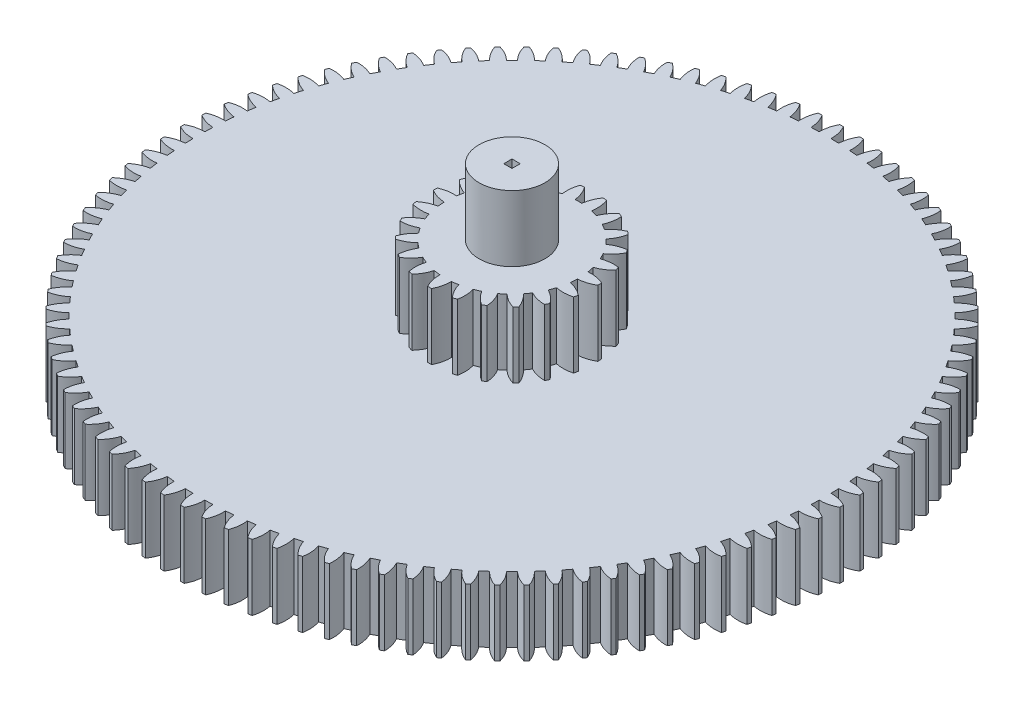
SolidWorks part; units mm, degrees
ref_plane "Front Plane" through (0, 0, 0) normal (0, 0, 1) x (1, 0, 0)
ref_plane "Top Plane" through (0, 0, 0) normal (0, 1, 0) x (1, 0, 0)
ref_plane "Right Plane" through (0, 0, 0) normal (1, 0, 0) x (0, 0, -1)
sketch "Sketch1" plane through (0, 0, 0) normal (0, 1, 0) x (1, 0, 0)
  arc A0 (-1.1228, 2.2337) -> (-1.1773, 2.2054) centre (0, 0) ccw
  arc A1 (-2.1122, 0.8038) -> (-2.1457, 0.7095) centre (0, 0) ccw
  arc A2 (0.05, 2.2594) -> (0.14, 2.4961) centre (0.4546, 2.241) cw
  arc A3 (-0.05, 2.2594) -> (-0.14, 2.4961) centre (-0.4546, 2.241) ccw
  arc A4 (0.3572, 2.2316) -> (0.4786, 2.4538) centre (0.7555, 2.1582) cw
  arc A5 (0.2581, 2.2452) -> (0.2012, 2.4919) centre (-0.1453, 2.282) ccw
  arc A6 (0.6577, 2.1622) -> (0.8082, 2.3657) centre (1.0424, 2.0352) cw
  arc A7 (0.5614, 2.1892) -> (0.5386, 2.4413) centre (0.1668, 2.2805) ccw
  arc A8 (0.946, 2.0525) -> (1.1228, 2.2337) centre (1.3098, 1.8743) cw
  arc A9 (0.8543, 2.0923) -> (0.866, 2.3452) centre (0.4758, 2.2366) ccw
  arc A10 (1.2167, 1.9045) -> (1.4165, 2.06) centre (1.5528, 1.6785) cw
  arc A11 (1.1313, 1.9565) -> (1.1773, 2.2054) centre (0.7759, 2.151) ccw
  arc A12 (1.4647, 1.7211) -> (1.6838, 1.8479) centre (1.7669, 1.4514) cw
  arc A13 (1.3871, 1.7842) -> (1.4666, 2.0246) centre (1.0616, 2.0253) ccw
  arc A14 (1.6854, 1.5057) -> (1.9198, 1.6014) centre (1.9481, 1.1973) cw
  arc A15 (1.6172, 1.5787) -> (1.7287, 1.806) centre (1.3275, 1.8619) ccw
  arc A16 (1.8747, 1.2621) -> (2.12, 1.3251) centre (2.093, 0.9209) cw
  arc A17 (1.8171, 1.3438) -> (1.9585, 1.5538) centre (1.5686, 1.6638) ccw
  arc A18 (2.0291, 0.9951) -> (2.2806, 1.0241) centre (2.1989, 0.6273) cw
  arc A19 (1.9831, 1.0839) -> (2.1518, 1.2727) centre (1.7806, 1.4347) ccw
  arc A20 (2.1457, 0.7095) -> (2.3988, 0.704) centre (2.2638, 0.3221) cw
  arc A21 (2.1122, 0.8038) -> (2.3051, 0.9678) centre (1.9593, 1.1788) ccw
  arc A22 (2.2224, 0.4107) -> (2.4724, 0.3708) centre (2.2866, 0.0108) cw
  arc A23 (2.202, 0.5087) -> (2.4154, 0.6449) centre (2.1016, 0.9011) ccw
  arc A24 (2.2576, 0.1043) -> (2.4998, 0.0307) centre (2.2668, -0.3006) cw
  arc A25 (2.2508, 0.2041) -> (2.4807, 0.31) centre (2.2047, 0.6065) ccw
  arc A26 (2.2508, -0.2041) -> (2.4807, -0.31) centre (2.2047, -0.6065) cw
  arc A27 (2.2576, -0.1043) -> (2.4998, -0.0307) centre (2.2668, 0.3006) ccw
  arc A28 (2.202, -0.5087) -> (2.4154, -0.6449) centre (2.1016, -0.9011) cw
  arc A29 (2.2224, -0.4107) -> (2.4724, -0.3708) centre (2.2866, -0.0108) ccw
  arc A30 (2.1122, -0.8038) -> (2.3051, -0.9678) centre (1.9593, -1.1788) cw
  arc A31 (2.1457, -0.7095) -> (2.3988, -0.704) centre (2.2638, -0.3221) ccw
  arc A32 (1.9831, -1.0839) -> (2.1518, -1.2727) centre (1.7806, -1.4347) cw
  arc A33 (2.0291, -0.9951) -> (2.2806, -1.0241) centre (2.1989, -0.6273) ccw
  arc A34 (1.8171, -1.3438) -> (1.9585, -1.5538) centre (1.5686, -1.6638) cw
  arc A35 (1.8747, -1.2621) -> (2.12, -1.3251) centre (2.093, -0.9209) ccw
  arc A36 (1.6172, -1.5787) -> (1.7287, -1.806) centre (1.3275, -1.8619) cw
  arc A37 (1.6854, -1.5057) -> (1.9198, -1.6014) centre (1.9481, -1.1973) ccw
  arc A38 (1.3871, -1.7842) -> (1.4666, -2.0246) centre (1.0616, -2.0253) cw
  arc A39 (1.4647, -1.7211) -> (1.6838, -1.8479) centre (1.7669, -1.4514) ccw
  arc A40 (1.1313, -1.9565) -> (1.1773, -2.2054) centre (0.7759, -2.151) cw
  arc A41 (1.2167, -1.9045) -> (1.4165, -2.06) centre (1.5528, -1.6785) ccw
  arc A42 (0.8543, -2.0923) -> (0.866, -2.3452) centre (0.4758, -2.2366) cw
  arc A43 (0.946, -2.0525) -> (1.1228, -2.2337) centre (1.3098, -1.8743) ccw
  arc A44 (0.5614, -2.1892) -> (0.5386, -2.4413) centre (0.1668, -2.2805) cw
  arc A45 (0.6577, -2.1622) -> (0.8082, -2.3657) centre (1.0424, -2.0352) ccw
  arc A46 (0.2581, -2.2452) -> (0.2012, -2.4919) centre (-0.1453, -2.282) cw
  arc A47 (0.3572, -2.2316) -> (0.4786, -2.4538) centre (0.7555, -2.1582) ccw
  arc A48 (-0.05, -2.2594) -> (-0.14, -2.4961) centre (-0.4546, -2.241) cw
  arc A49 (0.05, -2.2594) -> (0.14, -2.4961) centre (0.4546, -2.241) ccw
  arc A50 (-0.3572, -2.2316) -> (-0.4786, -2.4538) centre (-0.7555, -2.1582) cw
  arc A51 (-0.2581, -2.2452) -> (-0.2012, -2.4919) centre (0.1453, -2.282) ccw
  arc A52 (-0.6577, -2.1622) -> (-0.8082, -2.3657) centre (-1.0424, -2.0352) cw
  arc A53 (-0.5614, -2.1892) -> (-0.5386, -2.4413) centre (-0.1668, -2.2805) ccw
  arc A54 (-0.946, -2.0525) -> (-1.1228, -2.2337) centre (-1.3098, -1.8743) cw
  arc A55 (-0.8543, -2.0923) -> (-0.866, -2.3452) centre (-0.4758, -2.2366) ccw
  arc A56 (-1.2167, -1.9045) -> (-1.4165, -2.06) centre (-1.5528, -1.6785) cw
  arc A57 (-1.1313, -1.9565) -> (-1.1773, -2.2054) centre (-0.7759, -2.151) ccw
  arc A58 (-1.4647, -1.7211) -> (-1.6838, -1.8479) centre (-1.7669, -1.4514) cw
  arc A59 (-1.3871, -1.7842) -> (-1.4666, -2.0246) centre (-1.0616, -2.0253) ccw
  arc A60 (-1.6854, -1.5057) -> (-1.9198, -1.6014) centre (-1.9481, -1.1973) cw
  arc A61 (-1.6172, -1.5787) -> (-1.7287, -1.806) centre (-1.3275, -1.8619) ccw
  arc A62 (-1.8747, -1.2621) -> (-2.12, -1.3251) centre (-2.093, -0.9209) cw
  arc A63 (-1.8171, -1.3438) -> (-1.9585, -1.5538) centre (-1.5686, -1.6638) ccw
  arc A64 (-2.0291, -0.9951) -> (-2.2806, -1.0241) centre (-2.1989, -0.6273) cw
  arc A65 (-1.9831, -1.0839) -> (-2.1518, -1.2727) centre (-1.7806, -1.4347) ccw
  arc A66 (-2.1457, -0.7095) -> (-2.3988, -0.704) centre (-2.2638, -0.3221) cw
  arc A67 (-2.1122, -0.8038) -> (-2.3051, -0.9678) centre (-1.9593, -1.1788) ccw
  arc A68 (-2.2224, -0.4107) -> (-2.4724, -0.3708) centre (-2.2866, -0.0108) cw
  arc A69 (-2.202, -0.5087) -> (-2.4154, -0.6449) centre (-2.1016, -0.9011) ccw
  arc A70 (-2.2576, -0.1043) -> (-2.4998, -0.0307) centre (-2.2668, 0.3006) cw
  arc A71 (-2.2508, -0.2041) -> (-2.4807, -0.31) centre (-2.2047, -0.6065) ccw
  arc A72 (-2.2508, 0.2041) -> (-2.4807, 0.31) centre (-2.2047, 0.6065) cw
  arc A73 (-2.2576, 0.1043) -> (-2.4998, 0.0307) centre (-2.2668, -0.3006) ccw
  arc A74 (-2.202, 0.5087) -> (-2.4154, 0.6449) centre (-2.1016, 0.9011) cw
  arc A75 (-2.2224, 0.4107) -> (-2.4724, 0.3708) centre (-2.2866, 0.0108) ccw
  arc A76 (-2.1122, 0.8038) -> (-2.3051, 0.9678) centre (-1.9593, 1.1788) cw
  arc A77 (-2.1457, 0.7095) -> (-2.3988, 0.704) centre (-2.2638, 0.3221) ccw
  arc A78 (-1.9831, 1.0839) -> (-2.1518, 1.2727) centre (-1.7806, 1.4347) cw
  arc A79 (-2.0291, 0.9951) -> (-2.2806, 1.0241) centre (-2.1989, 0.6273) ccw
  arc A80 (-1.8171, 1.3438) -> (-1.9585, 1.5538) centre (-1.5686, 1.6638) cw
  arc A81 (-1.8747, 1.2621) -> (-2.12, 1.3251) centre (-2.093, 0.9209) ccw
  arc A82 (-1.6172, 1.5787) -> (-1.7287, 1.806) centre (-1.3275, 1.8619) cw
  arc A83 (-1.6854, 1.5057) -> (-1.9198, 1.6014) centre (-1.9481, 1.1973) ccw
  arc A84 (-1.3871, 1.7842) -> (-1.4666, 2.0246) centre (-1.0616, 2.0253) cw
  arc A85 (-1.4647, 1.7211) -> (-1.6838, 1.8479) centre (-1.7669, 1.4514) ccw
  arc A86 (-1.1313, 1.9565) -> (-1.1773, 2.2054) centre (-0.7759, 2.151) cw
  arc A87 (-1.2167, 1.9045) -> (-1.4165, 2.06) centre (-1.5528, 1.6785) ccw
  arc A88 (-0.8543, 2.0923) -> (-0.866, 2.3452) centre (-0.4758, 2.2366) cw
  arc A89 (-0.946, 2.0525) -> (-1.1228, 2.2337) centre (-1.3098, 1.8743) ccw
  arc A90 (-0.5614, 2.1892) -> (-0.5386, 2.4413) centre (-0.1668, 2.2805) cw
  arc A91 (-0.6577, 2.1622) -> (-0.8082, 2.3657) centre (-1.0424, 2.0352) ccw
  arc A92 (-0.2581, 2.2452) -> (-0.2012, 2.4919) centre (0.1453, 2.282) cw
  arc A93 (-0.3572, 2.2316) -> (-0.4786, 2.4538) centre (-0.7555, 2.1582) ccw
  arc A94 (-1.4165, 2.06) -> (-1.4666, 2.0246) centre (0, 0) ccw
  arc A95 (-1.6838, 1.8479) -> (-1.7287, 1.806) centre (0, 0) ccw
  arc A96 (-1.9198, 1.6014) -> (-1.9585, 1.5538) centre (0, 0) ccw
  arc A97 (-2.12, 1.3251) -> (-2.1518, 1.2727) centre (0, 0) ccw
  arc A98 (-2.2806, 1.0241) -> (-2.3051, 0.9678) centre (0, 0) ccw
  arc A99 (-2.3988, 0.704) -> (-2.4154, 0.6449) centre (0, 0) ccw
  arc A100 (-2.4724, 0.3708) -> (-2.4807, 0.31) centre (0, 0) ccw
  arc A101 (-2.4998, 0.0307) -> (-2.4998, -0.0307) centre (0, 0) ccw
  arc A102 (-2.4807, -0.31) -> (-2.4724, -0.3708) centre (0, 0) ccw
  arc A103 (-2.4154, -0.6449) -> (-2.3988, -0.704) centre (0, 0) ccw
  arc A104 (-2.3051, -0.9678) -> (-2.2806, -1.0241) centre (0, 0) ccw
  arc A105 (-2.1518, -1.2727) -> (-2.12, -1.3251) centre (0, 0) ccw
  arc A106 (-1.9585, -1.5538) -> (-1.9198, -1.6014) centre (0, 0) ccw
  arc A107 (-1.7287, -1.806) -> (-1.6838, -1.8479) centre (0, 0) ccw
  arc A108 (-1.4666, -2.0246) -> (-1.4165, -2.06) centre (0, 0) ccw
  arc A109 (-1.1773, -2.2054) -> (-1.1228, -2.2337) centre (0, 0) ccw
  arc A110 (-0.866, -2.3452) -> (-0.8082, -2.3657) centre (0, 0) ccw
  arc A111 (-0.5386, -2.4413) -> (-0.4786, -2.4538) centre (0, 0) ccw
  arc A112 (-0.2012, -2.4919) -> (-0.14, -2.4961) centre (0, 0) ccw
  arc A113 (0.14, -2.4961) -> (0.2012, -2.4919) centre (0, 0) ccw
  arc A114 (0.4786, -2.4538) -> (0.5386, -2.4413) centre (0, 0) ccw
  arc A115 (0.8082, -2.3657) -> (0.866, -2.3452) centre (0, 0) ccw
  arc A116 (1.1228, -2.2337) -> (1.1773, -2.2054) centre (0, 0) ccw
  arc A117 (1.4165, -2.06) -> (1.4666, -2.0246) centre (0, 0) ccw
  arc A118 (1.6838, -1.8479) -> (1.7287, -1.806) centre (0, 0) ccw
  arc A119 (1.9198, -1.6014) -> (1.9585, -1.5538) centre (0, 0) ccw
  arc A120 (2.12, -1.3251) -> (2.1518, -1.2727) centre (0, 0) ccw
  arc A121 (2.2806, -1.0241) -> (2.3051, -0.9678) centre (0, 0) ccw
  arc A122 (2.3988, -0.704) -> (2.4154, -0.6449) centre (0, 0) ccw
  arc A123 (2.4724, -0.3708) -> (2.4807, -0.31) centre (0, 0) ccw
  arc A124 (2.4998, -0.0307) -> (2.4998, 0.0307) centre (0, 0) ccw
  arc A125 (2.4807, 0.31) -> (2.4724, 0.3708) centre (0, 0) ccw
  arc A126 (2.4154, 0.6449) -> (2.3988, 0.704) centre (0, 0) ccw
  arc A127 (2.3051, 0.9678) -> (2.2806, 1.0241) centre (0, 0) ccw
  arc A128 (2.1518, 1.2727) -> (2.12, 1.3251) centre (0, 0) ccw
  arc A129 (1.9585, 1.5538) -> (1.9198, 1.6014) centre (0, 0) ccw
  arc A130 (1.7287, 1.806) -> (1.6838, 1.8479) centre (0, 0) ccw
  arc A131 (1.4666, 2.0246) -> (1.4165, 2.06) centre (0, 0) ccw
  arc A132 (1.1773, 2.2054) -> (1.1228, 2.2337) centre (0, 0) ccw
  arc A133 (0.866, 2.3452) -> (0.8082, 2.3657) centre (0, 0) ccw
  arc A134 (0.5386, 2.4413) -> (0.4786, 2.4538) centre (0, 0) ccw
  arc A135 (0.2012, 2.4919) -> (0.14, 2.4961) centre (0, 0) ccw
  arc A136 (-0.14, 2.4961) -> (-0.2012, 2.4919) centre (0, 0) ccw
  arc A137 (-0.4786, 2.4538) -> (-0.5386, 2.4413) centre (0, 0) ccw
  arc A138 (-0.8082, 2.3657) -> (-0.866, 2.3452) centre (0, 0) ccw
  arc A139 (-2.202, 0.5087) -> (-2.2224, 0.4107) centre (0, 0) ccw
  arc A140 (-2.2508, 0.2041) -> (-2.2576, 0.1043) centre (0, 0) ccw
  arc A141 (-2.2576, -0.1043) -> (-2.2508, -0.2041) centre (0, 0) ccw
  arc A142 (-2.2224, -0.4107) -> (-2.202, -0.5087) centre (0, 0) ccw
  arc A143 (-2.1457, -0.7095) -> (-2.1122, -0.8038) centre (0, 0) ccw
  arc A144 (-2.0291, -0.9951) -> (-1.9831, -1.0839) centre (0, 0) ccw
  arc A145 (-1.8747, -1.2621) -> (-1.8171, -1.3438) centre (0, 0) ccw
  arc A146 (-1.6854, -1.5057) -> (-1.6172, -1.5787) centre (0, 0) ccw
  arc A147 (-1.4647, -1.7211) -> (-1.3871, -1.7842) centre (0, 0) ccw
  arc A148 (-1.2167, -1.9045) -> (-1.1313, -1.9565) centre (0, 0) ccw
  arc A149 (-0.946, -2.0525) -> (-0.8543, -2.0923) centre (0, 0) ccw
  arc A150 (-0.6577, -2.1622) -> (-0.5614, -2.1892) centre (0, 0) ccw
  arc A151 (-0.3572, -2.2316) -> (-0.2581, -2.2452) centre (0, 0) ccw
  arc A152 (-0.05, -2.2594) -> (0.05, -2.2594) centre (0, 0) ccw
  arc A153 (0.2581, -2.2452) -> (0.3572, -2.2316) centre (0, 0) ccw
  arc A154 (0.5614, -2.1892) -> (0.6577, -2.1622) centre (0, 0) ccw
  arc A155 (0.8543, -2.0923) -> (0.946, -2.0525) centre (0, 0) ccw
  arc A156 (1.1313, -1.9565) -> (1.2167, -1.9045) centre (0, 0) ccw
  arc A157 (1.3871, -1.7842) -> (1.4647, -1.7211) centre (0, 0) ccw
  arc A158 (1.6172, -1.5787) -> (1.6854, -1.5057) centre (0, 0) ccw
  arc A159 (1.8171, -1.3438) -> (1.8747, -1.2621) centre (0, 0) ccw
  arc A160 (1.9831, -1.0839) -> (2.0291, -0.9951) centre (0, 0) ccw
  arc A161 (2.1122, -0.8038) -> (2.1457, -0.7095) centre (0, 0) ccw
  arc A162 (2.202, -0.5087) -> (2.2224, -0.4107) centre (0, 0) ccw
  arc A163 (2.2508, -0.2041) -> (2.2576, -0.1043) centre (0, 0) ccw
  arc A164 (2.2576, 0.1043) -> (2.2508, 0.2041) centre (0, 0) ccw
  arc A165 (2.2224, 0.4107) -> (2.202, 0.5087) centre (0, 0) ccw
  arc A166 (2.1457, 0.7095) -> (2.1122, 0.8038) centre (0, 0) ccw
  arc A167 (2.0291, 0.9951) -> (1.9831, 1.0839) centre (0, 0) ccw
  arc A168 (1.8747, 1.2621) -> (1.8171, 1.3438) centre (0, 0) ccw
  arc A169 (1.6854, 1.5057) -> (1.6172, 1.5787) centre (0, 0) ccw
  arc A170 (1.4647, 1.7211) -> (1.3871, 1.7842) centre (0, 0) ccw
  arc A171 (1.2167, 1.9045) -> (1.1313, 1.9565) centre (0, 0) ccw
  arc A172 (0.946, 2.0525) -> (0.8543, 2.0923) centre (0, 0) ccw
  arc A173 (0.6577, 2.1622) -> (0.5614, 2.1892) centre (0, 0) ccw
  arc A174 (0.3572, 2.2316) -> (0.2581, 2.2452) centre (0, 0) ccw
  arc A175 (0.05, 2.2594) -> (-0.05, 2.2594) centre (0, 0) ccw
  arc A176 (-1.3871, 1.7842) -> (-1.4647, 1.7211) centre (0, 0) ccw
  arc A177 (-1.1313, 1.9565) -> (-1.2167, 1.9045) centre (0, 0) ccw
  arc A178 (-0.8543, 2.0923) -> (-0.946, 2.0525) centre (0, 0) ccw
  arc A179 (-0.5614, 2.1892) -> (-0.6577, 2.1622) centre (0, 0) ccw
  arc A180 (-0.2581, 2.2452) -> (-0.3572, 2.2316) centre (0, 0) ccw
  arc A181 (-1.6172, 1.5787) -> (-1.6854, 1.5057) centre (0, 0) ccw
  arc A182 (-1.8171, 1.3438) -> (-1.8747, 1.2621) centre (0, 0) ccw
  arc A183 (-1.9831, 1.0839) -> (-2.0291, 0.9951) centre (0, 0) ccw
  point P4 (0, 2.26)
  point P5 (0, 2.5)
  point P285 (0, 0)
  dimension "D1" = 5
  dimension "D2" = 0.24
  dimension "D5" = 46
extrude "Boss-Extrude1" add sketch "Sketch1" along normal blind 1
sketch "Sketch2" plane through (0, 0, 0) normal (0, -1, 0) x (1, 0, 0)
  circle A0 centre (0, 0) radius 0.5
  dimension "D1" = 1
extrude "Boss-Extrude2" add sketch "Sketch2" along normal blind 2 and the other way blind 3
sketch "Sketch3" plane through (0, 1, 0) normal (0, 1, 0) x (1, 0, 0)
  arc A0 (-0.765, 0.9886) -> (-0.8122, 0.9501) centre (0, 0) ccw
  arc A1 (-0.4814, 0.8879) -> (-0.5669, 0.8359) centre (0, 0) ccw
  arc A2 (0.05, 1.0088) -> (0.14, 1.2421) centre (0.5621, 0.9453) cw
  arc A3 (-0.05, 1.0088) -> (-0.14, 1.2421) centre (-0.5621, 0.9453) ccw
  arc A4 (0.3203, 0.9579) -> (0.4699, 1.1583) centre (0.7963, 0.7586) cw
  arc A5 (0.224, 0.9848) -> (0.2003, 1.2338) centre (-0.2862, 1.0619) ccw
  arc A6 (0.5669, 0.8359) -> (0.765, 0.9886) centre (0.9714, 0.5157) cw
  arc A7 (0.4814, 0.8879) -> (0.5258, 1.134) centre (0.0109, 1.0997) ccw
  arc A8 (0.7714, 0.652) -> (1.0034, 0.7455) centre (1.0745, 0.2345) cw
  arc A9 (0.7031, 0.7251) -> (0.8122, 0.9501) centre (0.3072, 1.056) ccw
  arc A10 (0.9187, 0.4197) -> (1.1673, 0.4472) centre (1.0979, -0.0641) cw
  arc A11 (0.8727, 0.5085) -> (1.0385, 0.6958) centre (0.5808, 0.934) ccw
  arc A12 (0.9978, 0.1563) -> (1.2446, 0.1156) centre (1.0399, -0.358) cw
  arc A13 (0.9775, 0.2542) -> (1.1877, 0.3898) centre (0.8112, 0.7426) ccw
  arc A14 (1.003, -0.1187) -> (1.2297, -0.2244) centre (0.9048, -0.6253) cw
  arc A15 (1.0098, -0.019) -> (1.2488, 0.0549) centre (0.9815, 0.4962) ccw
  arc A16 (0.9338, -0.3849) -> (1.1235, -0.5479) centre (0.7025, -0.8462) cw
  arc A17 (0.9673, -0.2907) -> (1.2173, -0.284) centre (1.079, 0.213) ccw
  arc A18 (0.7953, -0.6226) -> (0.9341, -0.8307) centre (0.4482, -1.0043) cw
  arc A19 (0.853, -0.5409) -> (1.0955, -0.6019) centre (1.0964, -0.086) ccw
  arc A20 (0.5978, -0.8141) -> (0.6753, -1.0519) centre (0.1606, -1.088) cw
  arc A21 (0.6754, -0.751) -> (0.8925, -0.8752) centre (1.0326, -0.3786) ccw
  arc A22 (0.356, -0.9452) -> (0.3665, -1.1951) centre (-0.1389, -1.091) cw
  arc A23 (0.4478, -0.9053) -> (0.6233, -1.0835) centre (0.8922, -0.6431) ccw
  arc A24 (0.0878, -1.0062) -> (0.0304, -1.2496) centre (-0.4281, -1.0131) cw
  arc A25 (0.1869, -0.9926) -> (0.3078, -1.2115) centre (0.6856, -0.86) ccw
  arc A26 (-0.1869, -0.9926) -> (-0.3078, -1.2115) centre (-0.6856, -0.86) cw
  arc A27 (-0.0878, -1.0062) -> (-0.0304, -1.2496) centre (0.4281, -1.0131) ccw
  arc A28 (-0.4478, -0.9053) -> (-0.6233, -1.0835) centre (-0.8922, -0.6431) cw
  arc A29 (-0.356, -0.9452) -> (-0.3665, -1.1951) centre (0.1389, -1.091) ccw
  arc A30 (-0.6754, -0.751) -> (-0.8925, -0.8752) centre (-1.0326, -0.3786) cw
  arc A31 (-0.5978, -0.8141) -> (-0.6753, -1.0519) centre (-0.1606, -1.088) ccw
  arc A32 (-0.853, -0.5409) -> (-1.0955, -0.6019) centre (-1.0964, -0.086) cw
  arc A33 (-0.7953, -0.6226) -> (-0.9341, -0.8307) centre (-0.4482, -1.0043) ccw
  arc A34 (-0.9673, -0.2907) -> (-1.2173, -0.284) centre (-1.079, 0.213) cw
  arc A35 (-0.9338, -0.3849) -> (-1.1235, -0.5479) centre (-0.7025, -0.8462) ccw
  arc A36 (-1.0098, -0.019) -> (-1.2488, 0.0549) centre (-0.9815, 0.4962) cw
  arc A37 (-1.003, -0.1187) -> (-1.2297, -0.2244) centre (-0.9048, -0.6253) ccw
  arc A38 (-0.9775, 0.2542) -> (-1.1877, 0.3898) centre (-0.8112, 0.7426) cw
  arc A39 (-0.9978, 0.1563) -> (-1.2446, 0.1156) centre (-1.0399, -0.358) ccw
  arc A40 (-0.8727, 0.5085) -> (-1.0385, 0.6958) centre (-0.5808, 0.934) cw
  arc A41 (-0.9187, 0.4197) -> (-1.1673, 0.4472) centre (-1.0979, -0.0641) ccw
  arc A42 (-0.7031, 0.7251) -> (-0.8122, 0.9501) centre (-0.3072, 1.056) cw
  arc A43 (-0.7714, 0.652) -> (-1.0034, 0.7455) centre (-1.0745, 0.2345) ccw
  arc A44 (-0.4814, 0.8879) -> (-0.5258, 1.134) centre (-0.0109, 1.0997) cw
  arc A45 (-0.5669, 0.8359) -> (-0.765, 0.9886) centre (-0.9714, 0.5157) ccw
  arc A46 (-0.224, 0.9848) -> (-0.2003, 1.2338) centre (0.2862, 1.0619) cw
  arc A47 (-0.3203, 0.9579) -> (-0.4699, 1.1583) centre (-0.7963, 0.7586) ccw
  arc A48 (-1.0034, 0.7455) -> (-1.0385, 0.6958) centre (0, 0) ccw
  arc A49 (-1.2446, 0.1156) -> (-1.2488, 0.0549) centre (0, 0) ccw
  arc A50 (-1.1673, 0.4472) -> (-1.1877, 0.3898) centre (0, 0) ccw
  arc A51 (-1.2297, -0.2244) -> (-1.2173, -0.284) centre (0, 0) ccw
  arc A52 (-1.1235, -0.5479) -> (-1.0955, -0.6019) centre (0, 0) ccw
  arc A53 (-0.9341, -0.8307) -> (-0.8925, -0.8752) centre (0, 0) ccw
  arc A54 (-0.3665, -1.1951) -> (-0.3078, -1.2115) centre (0, 0) ccw
  arc A55 (-0.6753, -1.0519) -> (-0.6233, -1.0835) centre (0, 0) ccw
  arc A56 (-0.0304, -1.2496) -> (0.0304, -1.2496) centre (0, 0) ccw
  arc A57 (0.6233, -1.0835) -> (0.6753, -1.0519) centre (0, 0) ccw
  arc A58 (0.8925, -0.8752) -> (0.9341, -0.8307) centre (0, 0) ccw
  arc A59 (0.3078, -1.2115) -> (0.3665, -1.1951) centre (0, 0) ccw
  arc A60 (1.2173, -0.284) -> (1.2297, -0.2244) centre (0, 0) ccw
  arc A61 (1.0955, -0.6019) -> (1.1235, -0.5479) centre (0, 0) ccw
  arc A62 (1.2488, 0.0549) -> (1.2446, 0.1156) centre (0, 0) ccw
  arc A63 (1.1877, 0.3898) -> (1.1673, 0.4472) centre (0, 0) ccw
  arc A64 (1.0385, 0.6958) -> (1.0034, 0.7455) centre (0, 0) ccw
  arc A65 (0.8122, 0.9501) -> (0.765, 0.9886) centre (0, 0) ccw
  arc A66 (0.5258, 1.134) -> (0.4699, 1.1583) centre (0, 0) ccw
  arc A67 (0.2003, 1.2338) -> (0.14, 1.2421) centre (0, 0) ccw
  arc A68 (-0.4699, 1.1583) -> (-0.5258, 1.134) centre (0, 0) ccw
  arc A69 (-0.14, 1.2421) -> (-0.2003, 1.2338) centre (0, 0) ccw
  arc A70 (-0.7031, 0.7251) -> (-0.7714, 0.652) centre (0, 0) ccw
  arc A71 (-0.9775, 0.2542) -> (-0.9978, 0.1563) centre (0, 0) ccw
  arc A72 (-1.0098, -0.019) -> (-1.003, -0.1187) centre (0, 0) ccw
  arc A73 (-0.9673, -0.2907) -> (-0.9338, -0.3849) centre (0, 0) ccw
  arc A74 (-0.853, -0.5409) -> (-0.7953, -0.6226) centre (0, 0) ccw
  arc A75 (-0.224, 0.9848) -> (-0.3203, 0.9579) centre (0, 0) ccw
  arc A76 (0.05, 1.0088) -> (-0.05, 1.0088) centre (0, 0) ccw
  arc A77 (0.3203, 0.9579) -> (0.224, 0.9848) centre (0, 0) ccw
  arc A78 (0.5669, 0.8359) -> (0.4814, 0.8879) centre (0, 0) ccw
  arc A79 (0.7714, 0.652) -> (0.7031, 0.7251) centre (0, 0) ccw
  arc A80 (0.9187, 0.4197) -> (0.8727, 0.5085) centre (0, 0) ccw
  arc A81 (0.9978, 0.1563) -> (0.9775, 0.2542) centre (0, 0) ccw
  arc A82 (1.003, -0.1187) -> (1.0098, -0.019) centre (0, 0) ccw
  arc A83 (0.9338, -0.3849) -> (0.9673, -0.2907) centre (0, 0) ccw
  arc A84 (0.7953, -0.6226) -> (0.853, -0.5409) centre (0, 0) ccw
  arc A85 (0.5978, -0.8141) -> (0.6754, -0.751) centre (0, 0) ccw
  arc A86 (0.356, -0.9452) -> (0.4478, -0.9053) centre (0, 0) ccw
  arc A87 (0.0878, -1.0062) -> (0.1869, -0.9926) centre (0, 0) ccw
  arc A88 (-0.1869, -0.9926) -> (-0.0878, -1.0062) centre (0, 0) ccw
  arc A89 (-0.4478, -0.9053) -> (-0.356, -0.9452) centre (0, 0) ccw
  arc A90 (-0.6754, -0.751) -> (-0.5978, -0.8141) centre (0, 0) ccw
  arc A91 (-0.8727, 0.5085) -> (-0.9187, 0.4197) centre (0, 0) ccw
  point P4 (0, 1.25)
  point P5 (0, 1.01)
  point P147 (0, 0)
  dimension "D1" = 2.5
  dimension "D2" = 0.24
  dimension "D5" = 23
extrude "Boss-Extrude3" add sketch "Sketch3" along normal blind 1 contours A30 A90 A31 A55 A28 A89 A29 A54 A26 A88 A27 A56 A24 A87 A25 A59 A22 A86 A23 A57 A20 A85 A21 A58 A18 A84 A19 A61 A16 A83 A17 A60 A14 A82 A15 A62 A12 A81 A13 A63 A10 A80 A11 A64 A8 A79 A9 A65 A6 A78 A7 region at (0, 1, 0)
scale "Scale1" bodies to scale 103 scale about origin uniform scaling yes scale factor 2
sketch "Sketch4" plane through (0, 6, 0) normal (0, 1, 0) x (1, 0, 0)
  line L1 (-0.125, -0.125) -> (0.125, -0.125)
  line L2 (-0.125, -0.125) -> (-0.125, 0.125)
  line L3 (-0.125, 0.125) -> (0.125, 0.125)
  line L4 (0.125, -0.125) -> (0.125, 0.125)
  line L5 (-0.125, -0.125) -> (0.125, 0.125) construction
  line L6 (-0.125, 0.125) -> (0.125, -0.125) construction
  point P0 (0, 0)
  dimension "D1" = 0.25
  dimension "D2" = 0.25
extrude "Cut-Extrude1" cut sketch "Sketch4" against normal blind 1
sketch "Sketch5" plane through (0, -4, 0) normal (0, -1, 0) x (1, 0, 0)
  circle A0 centre (0, 0) radius 1
extrude "Cut-Extrude2" cut sketch "Sketch5" against normal blind 1.4
sketch "Sketch6" plane through (0, 0, 0) normal (0, -1, 0) x (1, 0, 0)
  circle A0 centre (0, 0) radius 1
  circle A1 centre (0, 0) radius 5
  dimension "D1" = 10
extrude "Cut-Extrude3" cut sketch "Sketch6" against normal blind 2
sketch "Sketch8" plane through (0, 2, 0) normal (0, -1, 0) x (1, 0, 0)
  line L0 (0, 0) -> (0, 0.18) construction
  line L1 (0, 0.18) -> (9.4983, 0.18) construction
  line L2 (0, 0) -> (0, -0.18) construction
  line L3 (0, -0.18) -> (9.4983, -0.18) construction
  arc A0 (9.9998, -0.0563) -> (9.9998, 0.0563) centre (0, 0) ccw
  arc A1 (9.4983, 0.18) -> (9.4909, 0.4168) centre (0, 0) ccw
  arc A2 (9.9998, 0.0563) -> (9.4983, 0.18) centre (9.5098, -0.8519) ccw
  arc A3 (9.9998, -0.0563) -> (9.4983, -0.18) centre (9.5098, 0.8519) cw
  arc A4 (9.9836, -0.5717) -> (9.4909, -0.4168) centre (9.4375, -1.4473) ccw
  arc A5 (9.9766, -0.6841) -> (9.9836, -0.5717) centre (0, 0) ccw
  arc A6 (9.9766, -0.6841) -> (9.4682, -0.776) centre (9.5445, 0.2531) cw
  arc A7 (9.928, -1.1975) -> (9.446, -1.0119) centre (9.328, -2.0371) ccw
  arc A8 (9.9139, -1.3091) -> (9.928, -1.1975) centre (0, 0) ccw
  arc A9 (9.9139, -1.3091) -> (9.4008, -1.369) centre (9.5416, -0.3467) cw
  arc A10 (9.8333, -1.8185) -> (9.3638, -1.603) centre (9.1817, -2.6188) ccw
  arc A11 (9.8122, -1.9291) -> (9.8333, -1.8185) centre (0, 0) ccw
  arc A12 (9.8122, -1.9291) -> (9.2963, -1.9566) centre (9.501, -0.9452) cw
  arc A13 (9.6997, -2.4324) -> (9.2447, -2.1878) centre (8.9991, -3.1901) ccw
  arc A14 (9.6717, -2.5414) -> (9.6997, -2.4324) centre (0, 0) ccw
  arc A15 (9.6717, -2.5414) -> (9.1551, -2.5365) centre (9.4229, -1.5399) cw
  arc A16 (9.5278, -3.0366) -> (9.089, -2.7639) centre (8.7811, -3.7489) ccw
  arc A17 (9.493, -3.1436) -> (9.5278, -3.0366) centre (0, 0) ccw
  arc A18 (9.493, -3.1436) -> (8.9778, -3.1063) centre (9.3076, -2.1285) cw
  arc A19 (9.3183, -3.6289) -> (8.8976, -3.3292) centre (8.5284, -4.2929) ccw
  arc A20 (9.2769, -3.7335) -> (9.3183, -3.6289) centre (0, 0) ccw
  arc A21 (9.2769, -3.7335) -> (8.765, -3.6639) centre (9.1556, -2.7087) cw
  arc A22 (9.0721, -4.2068) -> (8.671, -3.8813) centre (8.242, -4.8199) ccw
  arc A23 (9.0242, -4.3086) -> (9.0721, -4.2068) centre (0, 0) ccw
  arc A24 (9.0242, -4.3086) -> (8.5177, -4.207) centre (8.9674, -3.2782) cw
  arc A25 (8.79, -4.7681) -> (8.4101, -4.4181) centre (7.9231, -5.3279) ccw
  arc A26 (8.7358, -4.8668) -> (8.79, -4.7681) centre (0, 0) ccw
  arc A27 (8.7358, -4.8668) -> (8.2367, -4.7336) centre (8.7439, -3.8348) cw
  arc A28 (8.4733, -5.3107) -> (8.1161, -4.9375) centre (7.5729, -5.8149) ccw
  arc A29 (8.413, -5.4057) -> (8.4733, -5.3107) centre (0, 0) ccw
  arc A30 (8.413, -5.4057) -> (7.9232, -5.2414) centre (8.4858, -4.3763) cw
  arc A31 (8.1231, -5.8322) -> (7.7901, -5.4373) centre (7.1928, -6.2789) ccw
  arc A32 (8.057, -5.9233) -> (8.1231, -5.8322) centre (0, 0) ccw
  arc A33 (8.057, -5.9233) -> (7.5785, -5.7286) centre (8.1943, -4.9005) cw
  arc A34 (7.7409, -6.3308) -> (7.4333, -5.9157) centre (6.7844, -6.7182) ccw
  arc A35 (7.6691, -6.4175) -> (7.7409, -6.3308) centre (0, 0) ccw
  arc A36 (7.6691, -6.4175) -> (7.2038, -6.1931) centre (7.8704, -5.4054) cw
  arc A37 (7.3281, -6.8043) -> (7.0472, -6.3708) centre (6.3492, -7.1309) ccw
  arc A38 (7.251, -6.8864) -> (7.3281, -6.8043) centre (0, 0) ccw
  arc A39 (7.251, -6.8864) -> (6.8007, -6.6332) centre (7.5155, -5.8889) cw
  arc A40 (6.8864, -7.251) -> (6.6332, -6.8007) centre (5.8889, -7.5155) ccw
  arc A41 (6.8043, -7.3281) -> (6.8864, -7.251) centre (0, 0) ccw
  arc A42 (6.8043, -7.3281) -> (6.3708, -7.0472) centre (7.1309, -6.3492) cw
  arc A43 (6.4175, -7.6691) -> (6.1931, -7.2038) centre (5.4054, -7.8704) ccw
  arc A44 (6.3308, -7.7409) -> (6.4175, -7.6691) centre (0, 0) ccw
  arc A45 (6.3308, -7.7409) -> (5.9157, -7.4333) centre (6.7182, -6.7844) cw
  arc A46 (5.9233, -8.057) -> (5.7286, -7.5785) centre (4.9005, -8.1943) ccw
  arc A47 (5.8322, -8.1231) -> (5.9233, -8.057) centre (0, 0) ccw
  arc A48 (5.8322, -8.1231) -> (5.4373, -7.7901) centre (6.2789, -7.1928) cw
  arc A49 (5.4057, -8.413) -> (5.2414, -7.9232) centre (4.3763, -8.4858) ccw
  arc A50 (5.3107, -8.4733) -> (5.4057, -8.413) centre (0, 0) ccw
  arc A51 (5.3107, -8.4733) -> (4.9375, -8.1161) centre (5.8149, -7.5729) cw
  arc A52 (4.8668, -8.7358) -> (4.7336, -8.2367) centre (3.8348, -8.7439) ccw
  arc A53 (4.7681, -8.79) -> (4.8668, -8.7358) centre (0, 0) ccw
  arc A54 (4.7681, -8.79) -> (4.4181, -8.4101) centre (5.3279, -7.9231) cw
  arc A55 (4.3086, -9.0242) -> (4.207, -8.5177) centre (3.2782, -8.9674) ccw
  arc A56 (4.2068, -9.0721) -> (4.3086, -9.0242) centre (0, 0) ccw
  arc A57 (4.2068, -9.0721) -> (3.8813, -8.671) centre (4.8199, -8.242) cw
  arc A58 (3.7335, -9.2769) -> (3.6639, -8.765) centre (2.7087, -9.1556) ccw
  arc A59 (3.6289, -9.3183) -> (3.7335, -9.2769) centre (0, 0) ccw
  arc A60 (3.6289, -9.3183) -> (3.3292, -8.8976) centre (4.2929, -8.5284) cw
  arc A61 (3.1436, -9.493) -> (3.1063, -8.9778) centre (2.1285, -9.3076) ccw
  arc A62 (3.0366, -9.5278) -> (3.1436, -9.493) centre (0, 0) ccw
  arc A63 (3.0366, -9.5278) -> (2.7639, -9.089) centre (3.7489, -8.7811) cw
  arc A64 (2.5414, -9.6717) -> (2.5365, -9.1551) centre (1.5399, -9.4229) ccw
  arc A65 (2.4324, -9.6997) -> (2.5414, -9.6717) centre (0, 0) ccw
  arc A66 (2.4324, -9.6997) -> (2.1878, -9.2447) centre (3.1901, -8.9991) cw
  arc A67 (1.9291, -9.8122) -> (1.9566, -9.2963) centre (0.9452, -9.501) ccw
  arc A68 (1.8185, -9.8333) -> (1.9291, -9.8122) centre (0, 0) ccw
  arc A69 (1.8185, -9.8333) -> (1.603, -9.3638) centre (2.6188, -9.1817) cw
  arc A70 (1.3091, -9.9139) -> (1.369, -9.4008) centre (0.3467, -9.5416) ccw
  arc A71 (1.1975, -9.928) -> (1.3091, -9.9139) centre (0, 0) ccw
  arc A72 (1.1975, -9.928) -> (1.0119, -9.446) centre (2.0371, -9.328) cw
  arc A73 (0.6841, -9.9766) -> (0.776, -9.4682) centre (-0.2531, -9.5445) ccw
  arc A74 (0.5717, -9.9836) -> (0.6841, -9.9766) centre (0, 0) ccw
  arc A75 (0.5717, -9.9836) -> (0.4168, -9.4909) centre (1.4473, -9.4375) cw
  arc A76 (0.0563, -9.9998) -> (0.18, -9.4983) centre (-0.8519, -9.5098) ccw
  arc A77 (-0.0563, -9.9998) -> (0.0563, -9.9998) centre (0, 0) ccw
  arc A78 (-0.0563, -9.9998) -> (-0.18, -9.4983) centre (0.8519, -9.5098) cw
  arc A79 (-0.5717, -9.9836) -> (-0.4168, -9.4909) centre (-1.4473, -9.4375) ccw
  arc A80 (-0.6841, -9.9766) -> (-0.5717, -9.9836) centre (0, 0) ccw
  arc A81 (-0.6841, -9.9766) -> (-0.776, -9.4682) centre (0.2531, -9.5445) cw
  arc A82 (-1.1975, -9.928) -> (-1.0119, -9.446) centre (-2.0371, -9.328) ccw
  arc A83 (-1.3091, -9.9139) -> (-1.1975, -9.928) centre (0, 0) ccw
  arc A84 (-1.3091, -9.9139) -> (-1.369, -9.4008) centre (-0.3467, -9.5416) cw
  arc A85 (-1.8185, -9.8333) -> (-1.603, -9.3638) centre (-2.6188, -9.1817) ccw
  arc A86 (-1.9291, -9.8122) -> (-1.8185, -9.8333) centre (0, 0) ccw
  arc A87 (-1.9291, -9.8122) -> (-1.9566, -9.2963) centre (-0.9452, -9.501) cw
  arc A88 (-2.4324, -9.6997) -> (-2.1878, -9.2447) centre (-3.1901, -8.9991) ccw
  arc A89 (-2.5414, -9.6717) -> (-2.4324, -9.6997) centre (0, 0) ccw
  arc A90 (-2.5414, -9.6717) -> (-2.5365, -9.1551) centre (-1.5399, -9.4229) cw
  arc A91 (-3.0366, -9.5278) -> (-2.7639, -9.089) centre (-3.7489, -8.7811) ccw
  arc A92 (-3.1436, -9.493) -> (-3.0366, -9.5278) centre (0, 0) ccw
  arc A93 (-3.1436, -9.493) -> (-3.1063, -8.9778) centre (-2.1285, -9.3076) cw
  arc A94 (-3.6289, -9.3183) -> (-3.3292, -8.8976) centre (-4.2929, -8.5284) ccw
  arc A95 (-3.7335, -9.2769) -> (-3.6289, -9.3183) centre (0, 0) ccw
  arc A96 (-3.7335, -9.2769) -> (-3.6639, -8.765) centre (-2.7087, -9.1556) cw
  arc A97 (-4.2068, -9.0721) -> (-3.8813, -8.671) centre (-4.8199, -8.242) ccw
  arc A98 (-4.3086, -9.0242) -> (-4.2068, -9.0721) centre (0, 0) ccw
  arc A99 (-4.3086, -9.0242) -> (-4.207, -8.5177) centre (-3.2782, -8.9674) cw
  arc A100 (-4.7681, -8.79) -> (-4.4181, -8.4101) centre (-5.3279, -7.9231) ccw
  arc A101 (-4.8668, -8.7358) -> (-4.7681, -8.79) centre (0, 0) ccw
  arc A102 (-4.8668, -8.7358) -> (-4.7336, -8.2367) centre (-3.8348, -8.7439) cw
  arc A103 (-5.3107, -8.4733) -> (-4.9375, -8.1161) centre (-5.8149, -7.5729) ccw
  arc A104 (-5.4057, -8.413) -> (-5.3107, -8.4733) centre (0, 0) ccw
  arc A105 (-5.4057, -8.413) -> (-5.2414, -7.9232) centre (-4.3763, -8.4858) cw
  arc A106 (-5.8322, -8.1231) -> (-5.4373, -7.7901) centre (-6.2789, -7.1928) ccw
  arc A107 (-5.9233, -8.057) -> (-5.8322, -8.1231) centre (0, 0) ccw
  arc A108 (-5.9233, -8.057) -> (-5.7286, -7.5785) centre (-4.9005, -8.1943) cw
  arc A109 (-6.3308, -7.7409) -> (-5.9157, -7.4333) centre (-6.7182, -6.7844) ccw
  arc A110 (-6.4175, -7.6691) -> (-6.3308, -7.7409) centre (0, 0) ccw
  arc A111 (-6.4175, -7.6691) -> (-6.1931, -7.2038) centre (-5.4054, -7.8704) cw
  arc A112 (-6.8043, -7.3281) -> (-6.3708, -7.0472) centre (-7.1309, -6.3492) ccw
  arc A113 (-6.8864, -7.251) -> (-6.8043, -7.3281) centre (0, 0) ccw
  arc A114 (-6.8864, -7.251) -> (-6.6332, -6.8007) centre (-5.8889, -7.5155) cw
  arc A115 (-7.251, -6.8864) -> (-6.8007, -6.6332) centre (-7.5155, -5.8889) ccw
  arc A116 (-7.3281, -6.8043) -> (-7.251, -6.8864) centre (0, 0) ccw
  arc A117 (-7.3281, -6.8043) -> (-7.0472, -6.3708) centre (-6.3492, -7.1309) cw
  arc A118 (-7.6691, -6.4175) -> (-7.2038, -6.1931) centre (-7.8704, -5.4054) ccw
  arc A119 (-7.7409, -6.3308) -> (-7.6691, -6.4175) centre (0, 0) ccw
  arc A120 (-7.7409, -6.3308) -> (-7.4333, -5.9157) centre (-6.7844, -6.7182) cw
  arc A121 (-8.057, -5.9233) -> (-7.5785, -5.7286) centre (-8.1943, -4.9005) ccw
  arc A122 (-8.1231, -5.8322) -> (-8.057, -5.9233) centre (0, 0) ccw
  arc A123 (-8.1231, -5.8322) -> (-7.7901, -5.4373) centre (-7.1928, -6.2789) cw
  arc A124 (-8.413, -5.4057) -> (-7.9232, -5.2414) centre (-8.4858, -4.3763) ccw
  arc A125 (-8.4733, -5.3107) -> (-8.413, -5.4057) centre (0, 0) ccw
  arc A126 (-8.4733, -5.3107) -> (-8.1161, -4.9375) centre (-7.5729, -5.8149) cw
  arc A127 (-8.7358, -4.8668) -> (-8.2367, -4.7336) centre (-8.7439, -3.8348) ccw
  arc A128 (-8.79, -4.7681) -> (-8.7358, -4.8668) centre (0, 0) ccw
  arc A129 (-8.79, -4.7681) -> (-8.4101, -4.4181) centre (-7.9231, -5.3279) cw
  arc A130 (-9.0242, -4.3086) -> (-8.5177, -4.207) centre (-8.9674, -3.2782) ccw
  arc A131 (-9.0721, -4.2068) -> (-9.0242, -4.3086) centre (0, 0) ccw
  arc A132 (-9.0721, -4.2068) -> (-8.671, -3.8813) centre (-8.242, -4.8199) cw
  arc A133 (-9.2769, -3.7335) -> (-8.765, -3.6639) centre (-9.1556, -2.7087) ccw
  arc A134 (-9.3183, -3.6289) -> (-9.2769, -3.7335) centre (0, 0) ccw
  arc A135 (-9.3183, -3.6289) -> (-8.8976, -3.3292) centre (-8.5284, -4.2929) cw
  arc A136 (-9.493, -3.1436) -> (-8.9778, -3.1063) centre (-9.3076, -2.1285) ccw
  arc A137 (-9.5278, -3.0366) -> (-9.493, -3.1436) centre (0, 0) ccw
  arc A138 (-9.5278, -3.0366) -> (-9.089, -2.7639) centre (-8.7811, -3.7489) cw
  arc A139 (-9.6717, -2.5414) -> (-9.1551, -2.5365) centre (-9.4229, -1.5399) ccw
  arc A140 (-9.6997, -2.4324) -> (-9.6717, -2.5414) centre (0, 0) ccw
  arc A141 (-9.6997, -2.4324) -> (-9.2447, -2.1878) centre (-8.9991, -3.1901) cw
  arc A142 (-9.8122, -1.9291) -> (-9.2963, -1.9566) centre (-9.501, -0.9452) ccw
  arc A143 (-9.8333, -1.8185) -> (-9.8122, -1.9291) centre (0, 0) ccw
  arc A144 (-9.8333, -1.8185) -> (-9.3638, -1.603) centre (-9.1817, -2.6188) cw
  arc A145 (-9.9139, -1.3091) -> (-9.4008, -1.369) centre (-9.5416, -0.3467) ccw
  arc A146 (-9.928, -1.1975) -> (-9.9139, -1.3091) centre (0, 0) ccw
  arc A147 (-9.928, -1.1975) -> (-9.446, -1.0119) centre (-9.328, -2.0371) cw
  arc A148 (-9.9766, -0.6841) -> (-9.4682, -0.776) centre (-9.5445, 0.2531) ccw
  arc A149 (-9.9836, -0.5717) -> (-9.9766, -0.6841) centre (0, 0) ccw
  arc A150 (-9.9836, -0.5717) -> (-9.4909, -0.4168) centre (-9.4375, -1.4473) cw
  arc A151 (-9.9998, -0.0563) -> (-9.4983, -0.18) centre (-9.5098, 0.8519) ccw
  arc A152 (-9.9998, 0.0563) -> (-9.9998, -0.0563) centre (0, 0) ccw
  arc A153 (-9.9998, 0.0563) -> (-9.4983, 0.18) centre (-9.5098, -0.8519) cw
  arc A154 (-9.9836, 0.5717) -> (-9.4909, 0.4168) centre (-9.4375, 1.4473) ccw
  arc A155 (-9.9766, 0.6841) -> (-9.9836, 0.5717) centre (0, 0) ccw
  arc A156 (-9.9766, 0.6841) -> (-9.4682, 0.776) centre (-9.5445, -0.2531) cw
  arc A157 (-9.928, 1.1975) -> (-9.446, 1.0119) centre (-9.328, 2.0371) ccw
  arc A158 (-9.9139, 1.3091) -> (-9.928, 1.1975) centre (0, 0) ccw
  arc A159 (-9.9139, 1.3091) -> (-9.4008, 1.369) centre (-9.5416, 0.3467) cw
  arc A160 (-9.8333, 1.8185) -> (-9.3638, 1.603) centre (-9.1817, 2.6188) ccw
  arc A161 (-9.8122, 1.9291) -> (-9.8333, 1.8185) centre (0, 0) ccw
  arc A162 (-9.8122, 1.9291) -> (-9.2963, 1.9566) centre (-9.501, 0.9452) cw
  arc A163 (-9.6997, 2.4324) -> (-9.2447, 2.1878) centre (-8.9991, 3.1901) ccw
  arc A164 (-9.6717, 2.5414) -> (-9.6997, 2.4324) centre (0, 0) ccw
  arc A165 (-9.6717, 2.5414) -> (-9.1551, 2.5365) centre (-9.4229, 1.5399) cw
  arc A166 (-9.5278, 3.0366) -> (-9.089, 2.7639) centre (-8.7811, 3.7489) ccw
  arc A167 (-9.493, 3.1436) -> (-9.5278, 3.0366) centre (0, 0) ccw
  arc A168 (-9.493, 3.1436) -> (-8.9778, 3.1063) centre (-9.3076, 2.1285) cw
  arc A169 (-9.3183, 3.6289) -> (-8.8976, 3.3292) centre (-8.5284, 4.2929) ccw
  arc A170 (-9.2769, 3.7335) -> (-9.3183, 3.6289) centre (0, 0) ccw
  arc A171 (-9.2769, 3.7335) -> (-8.765, 3.6639) centre (-9.1556, 2.7087) cw
  arc A172 (-9.0721, 4.2068) -> (-8.671, 3.8813) centre (-8.242, 4.8199) ccw
  arc A173 (-9.0242, 4.3086) -> (-9.0721, 4.2068) centre (0, 0) ccw
  arc A174 (-9.0242, 4.3086) -> (-8.5177, 4.207) centre (-8.9674, 3.2782) cw
  arc A175 (-8.79, 4.7681) -> (-8.4101, 4.4181) centre (-7.9231, 5.3279) ccw
  arc A176 (-8.7358, 4.8668) -> (-8.79, 4.7681) centre (0, 0) ccw
  arc A177 (-8.7358, 4.8668) -> (-8.2367, 4.7336) centre (-8.7439, 3.8348) cw
  arc A178 (-8.4733, 5.3107) -> (-8.1161, 4.9375) centre (-7.5729, 5.8149) ccw
  arc A179 (-8.413, 5.4057) -> (-8.4733, 5.3107) centre (0, 0) ccw
  arc A180 (-8.413, 5.4057) -> (-7.9232, 5.2414) centre (-8.4858, 4.3763) cw
  arc A181 (-8.1231, 5.8322) -> (-7.7901, 5.4373) centre (-7.1928, 6.2789) ccw
  arc A182 (-8.057, 5.9233) -> (-8.1231, 5.8322) centre (0, 0) ccw
  arc A183 (-8.057, 5.9233) -> (-7.5785, 5.7286) centre (-8.1943, 4.9005) cw
  arc A184 (-7.7409, 6.3308) -> (-7.4333, 5.9157) centre (-6.7844, 6.7182) ccw
  arc A185 (-7.6691, 6.4175) -> (-7.7409, 6.3308) centre (0, 0) ccw
  arc A186 (-7.6691, 6.4175) -> (-7.2038, 6.1931) centre (-7.8704, 5.4054) cw
  arc A187 (-7.3281, 6.8043) -> (-7.0472, 6.3708) centre (-6.3492, 7.1309) ccw
  arc A188 (-7.251, 6.8864) -> (-7.3281, 6.8043) centre (0, 0) ccw
  arc A189 (-7.251, 6.8864) -> (-6.8007, 6.6332) centre (-7.5155, 5.8889) cw
  arc A190 (-6.8864, 7.251) -> (-6.6332, 6.8007) centre (-5.8889, 7.5155) ccw
  arc A191 (-6.8043, 7.3281) -> (-6.8864, 7.251) centre (0, 0) ccw
  arc A192 (-6.8043, 7.3281) -> (-6.3708, 7.0472) centre (-7.1309, 6.3492) cw
  arc A193 (-6.4175, 7.6691) -> (-6.1931, 7.2038) centre (-5.4054, 7.8704) ccw
  arc A194 (-6.3308, 7.7409) -> (-6.4175, 7.6691) centre (0, 0) ccw
  arc A195 (-6.3308, 7.7409) -> (-5.9157, 7.4333) centre (-6.7182, 6.7844) cw
  arc A196 (-5.9233, 8.057) -> (-5.7286, 7.5785) centre (-4.9005, 8.1943) ccw
  arc A197 (-5.8322, 8.1231) -> (-5.9233, 8.057) centre (0, 0) ccw
  arc A198 (-5.8322, 8.1231) -> (-5.4373, 7.7901) centre (-6.2789, 7.1928) cw
  arc A199 (-5.4057, 8.413) -> (-5.2414, 7.9232) centre (-4.3763, 8.4858) ccw
  arc A200 (-5.3107, 8.4733) -> (-5.4057, 8.413) centre (0, 0) ccw
  arc A201 (-5.3107, 8.4733) -> (-4.9375, 8.1161) centre (-5.8149, 7.5729) cw
  arc A202 (-4.8668, 8.7358) -> (-4.7336, 8.2367) centre (-3.8348, 8.7439) ccw
  arc A203 (-4.7681, 8.79) -> (-4.8668, 8.7358) centre (0, 0) ccw
  arc A204 (-4.7681, 8.79) -> (-4.4181, 8.4101) centre (-5.3279, 7.9231) cw
  arc A205 (-4.3086, 9.0242) -> (-4.207, 8.5177) centre (-3.2782, 8.9674) ccw
  arc A206 (-4.2068, 9.0721) -> (-4.3086, 9.0242) centre (0, 0) ccw
  arc A207 (-4.2068, 9.0721) -> (-3.8813, 8.671) centre (-4.8199, 8.242) cw
  arc A208 (-3.7335, 9.2769) -> (-3.6639, 8.765) centre (-2.7087, 9.1556) ccw
  arc A209 (-3.6289, 9.3183) -> (-3.7335, 9.2769) centre (0, 0) ccw
  arc A210 (-3.6289, 9.3183) -> (-3.3292, 8.8976) centre (-4.2929, 8.5284) cw
  arc A211 (-3.1436, 9.493) -> (-3.1063, 8.9778) centre (-2.1285, 9.3076) ccw
  arc A212 (-3.0366, 9.5278) -> (-3.1436, 9.493) centre (0, 0) ccw
  arc A213 (-3.0366, 9.5278) -> (-2.7639, 9.089) centre (-3.7489, 8.7811) cw
  arc A214 (-2.5414, 9.6717) -> (-2.5365, 9.1551) centre (-1.5399, 9.4229) ccw
  arc A215 (-2.4324, 9.6997) -> (-2.5414, 9.6717) centre (0, 0) ccw
  arc A216 (-2.4324, 9.6997) -> (-2.1878, 9.2447) centre (-3.1901, 8.9991) cw
  arc A217 (-1.9291, 9.8122) -> (-1.9566, 9.2963) centre (-0.9452, 9.501) ccw
  arc A218 (-1.8185, 9.8333) -> (-1.9291, 9.8122) centre (0, 0) ccw
  arc A219 (-1.8185, 9.8333) -> (-1.603, 9.3638) centre (-2.6188, 9.1817) cw
  arc A220 (-1.3091, 9.9139) -> (-1.369, 9.4008) centre (-0.3467, 9.5416) ccw
  arc A221 (-1.1975, 9.928) -> (-1.3091, 9.9139) centre (0, 0) ccw
  arc A222 (-1.1975, 9.928) -> (-1.0119, 9.446) centre (-2.0371, 9.328) cw
  arc A223 (-0.6841, 9.9766) -> (-0.776, 9.4682) centre (0.2531, 9.5445) ccw
  arc A224 (-0.5717, 9.9836) -> (-0.6841, 9.9766) centre (0, 0) ccw
  arc A225 (-0.5717, 9.9836) -> (-0.4168, 9.4909) centre (-1.4473, 9.4375) cw
  arc A226 (-0.0563, 9.9998) -> (-0.18, 9.4983) centre (0.8519, 9.5098) ccw
  arc A227 (0.0563, 9.9998) -> (-0.0563, 9.9998) centre (0, 0) ccw
  arc A228 (0.0563, 9.9998) -> (0.18, 9.4983) centre (-0.8519, 9.5098) cw
  arc A229 (0.5717, 9.9836) -> (0.4168, 9.4909) centre (1.4473, 9.4375) ccw
  arc A230 (0.6841, 9.9766) -> (0.5717, 9.9836) centre (0, 0) ccw
  arc A231 (0.6841, 9.9766) -> (0.776, 9.4682) centre (-0.2531, 9.5445) cw
  arc A232 (1.1975, 9.928) -> (1.0119, 9.446) centre (2.0371, 9.328) ccw
  arc A233 (1.3091, 9.9139) -> (1.1975, 9.928) centre (0, 0) ccw
  arc A234 (1.3091, 9.9139) -> (1.369, 9.4008) centre (0.3467, 9.5416) cw
  arc A235 (1.8185, 9.8333) -> (1.603, 9.3638) centre (2.6188, 9.1817) ccw
  arc A236 (1.9291, 9.8122) -> (1.8185, 9.8333) centre (0, 0) ccw
  arc A237 (1.9291, 9.8122) -> (1.9566, 9.2963) centre (0.9452, 9.501) cw
  arc A238 (2.4324, 9.6997) -> (2.1878, 9.2447) centre (3.1901, 8.9991) ccw
  arc A239 (2.5414, 9.6717) -> (2.4324, 9.6997) centre (0, 0) ccw
  arc A240 (2.5414, 9.6717) -> (2.5365, 9.1551) centre (1.5399, 9.4229) cw
  arc A241 (3.0366, 9.5278) -> (2.7639, 9.089) centre (3.7489, 8.7811) ccw
  arc A242 (3.1436, 9.493) -> (3.0366, 9.5278) centre (0, 0) ccw
  arc A243 (3.1436, 9.493) -> (3.1063, 8.9778) centre (2.1285, 9.3076) cw
  arc A244 (3.6289, 9.3183) -> (3.3292, 8.8976) centre (4.2929, 8.5284) ccw
  arc A245 (3.7335, 9.2769) -> (3.6289, 9.3183) centre (0, 0) ccw
  arc A246 (3.7335, 9.2769) -> (3.6639, 8.765) centre (2.7087, 9.1556) cw
  arc A247 (4.2068, 9.0721) -> (3.8813, 8.671) centre (4.8199, 8.242) ccw
  arc A248 (4.3086, 9.0242) -> (4.2068, 9.0721) centre (0, 0) ccw
  arc A249 (4.3086, 9.0242) -> (4.207, 8.5177) centre (3.2782, 8.9674) cw
  arc A250 (4.7681, 8.79) -> (4.4181, 8.4101) centre (5.3279, 7.9231) ccw
  arc A251 (4.8668, 8.7358) -> (4.7681, 8.79) centre (0, 0) ccw
  arc A252 (4.8668, 8.7358) -> (4.7336, 8.2367) centre (3.8348, 8.7439) cw
  arc A253 (5.3107, 8.4733) -> (4.9375, 8.1161) centre (5.8149, 7.5729) ccw
  arc A254 (5.4057, 8.413) -> (5.3107, 8.4733) centre (0, 0) ccw
  arc A255 (5.4057, 8.413) -> (5.2414, 7.9232) centre (4.3763, 8.4858) cw
  arc A256 (5.8322, 8.1231) -> (5.4373, 7.7901) centre (6.2789, 7.1928) ccw
  arc A257 (5.9233, 8.057) -> (5.8322, 8.1231) centre (0, 0) ccw
  arc A258 (5.9233, 8.057) -> (5.7286, 7.5785) centre (4.9005, 8.1943) cw
  arc A259 (6.3308, 7.7409) -> (5.9157, 7.4333) centre (6.7182, 6.7844) ccw
  arc A260 (6.4175, 7.6691) -> (6.3308, 7.7409) centre (0, 0) ccw
  arc A261 (6.4175, 7.6691) -> (6.1931, 7.2038) centre (5.4054, 7.8704) cw
  arc A262 (6.8043, 7.3281) -> (6.3708, 7.0472) centre (7.1309, 6.3492) ccw
  arc A263 (6.8864, 7.251) -> (6.8043, 7.3281) centre (0, 0) ccw
  arc A264 (6.8864, 7.251) -> (6.6332, 6.8007) centre (5.8889, 7.5155) cw
  arc A265 (7.251, 6.8864) -> (6.8007, 6.6332) centre (7.5155, 5.8889) ccw
  arc A266 (7.3281, 6.8043) -> (7.251, 6.8864) centre (0, 0) ccw
  arc A267 (7.3281, 6.8043) -> (7.0472, 6.3708) centre (6.3492, 7.1309) cw
  arc A268 (7.6691, 6.4175) -> (7.2038, 6.1931) centre (7.8704, 5.4054) ccw
  arc A269 (7.7409, 6.3308) -> (7.6691, 6.4175) centre (0, 0) ccw
  arc A270 (7.7409, 6.3308) -> (7.4333, 5.9157) centre (6.7844, 6.7182) cw
  arc A271 (8.057, 5.9233) -> (7.5785, 5.7286) centre (8.1943, 4.9005) ccw
  arc A272 (8.1231, 5.8322) -> (8.057, 5.9233) centre (0, 0) ccw
  arc A273 (8.1231, 5.8322) -> (7.7901, 5.4373) centre (7.1928, 6.2789) cw
  arc A274 (8.413, 5.4057) -> (7.9232, 5.2414) centre (8.4858, 4.3763) ccw
  arc A275 (8.4733, 5.3107) -> (8.413, 5.4057) centre (0, 0) ccw
  arc A276 (8.4733, 5.3107) -> (8.1161, 4.9375) centre (7.5729, 5.8149) cw
  arc A277 (8.7358, 4.8668) -> (8.2367, 4.7336) centre (8.7439, 3.8348) ccw
  arc A278 (8.79, 4.7681) -> (8.7358, 4.8668) centre (0, 0) ccw
  arc A279 (8.79, 4.7681) -> (8.4101, 4.4181) centre (7.9231, 5.3279) cw
  arc A280 (9.4909, -0.4168) -> (9.4983, -0.18) centre (0, 0) ccw
  arc A281 (9.446, -1.0119) -> (9.4682, -0.776) centre (0, 0) ccw
  arc A282 (9.3638, -1.603) -> (9.4008, -1.369) centre (0, 0) ccw
  arc A283 (9.2447, -2.1878) -> (9.2963, -1.9566) centre (0, 0) ccw
  arc A284 (9.0242, 4.3086) -> (8.5177, 4.207) centre (8.9674, 3.2782) ccw
  arc A285 (9.0721, 4.2068) -> (9.0242, 4.3086) centre (0, 0) ccw
  arc A286 (9.0721, 4.2068) -> (8.671, 3.8813) centre (8.242, 4.8199) cw
  arc A287 (8.5177, 4.207) -> (8.4101, 4.4181) centre (0, 0) ccw
  arc A288 (8.2367, 4.7336) -> (8.1161, 4.9375) centre (0, 0) ccw
  arc A289 (7.9232, 5.2414) -> (7.7901, 5.4373) centre (0, 0) ccw
  arc A290 (-4.9375, -8.1161) -> (-4.7336, -8.2367) centre (0, 0) ccw
  arc A291 (-4.4181, -8.4101) -> (-4.207, -8.5177) centre (0, 0) ccw
  arc A292 (-3.8813, -8.671) -> (-3.6639, -8.765) centre (0, 0) ccw
  arc A293 (-3.3292, -8.8976) -> (-3.1063, -8.9778) centre (0, 0) ccw
  arc A294 (-5.4373, -7.7901) -> (-5.2414, -7.9232) centre (0, 0) ccw
  arc A295 (-5.9157, -7.4333) -> (-5.7286, -7.5785) centre (0, 0) ccw
  arc A296 (-6.3708, -7.0472) -> (-6.1931, -7.2038) centre (0, 0) ccw
  arc A297 (-6.8007, -6.6332) -> (-6.6332, -6.8007) centre (0, 0) ccw
  arc A298 (-7.5785, -5.7286) -> (-7.4333, -5.9157) centre (0, 0) ccw
  arc A299 (-7.2038, -6.1931) -> (-7.0472, -6.3708) centre (0, 0) ccw
  arc A300 (-7.9232, -5.2414) -> (-7.7901, -5.4373) centre (0, 0) ccw
  arc A301 (-8.2367, -4.7336) -> (-8.1161, -4.9375) centre (0, 0) ccw
  arc A302 (-8.5177, -4.207) -> (-8.4101, -4.4181) centre (0, 0) ccw
  arc A303 (-2.1878, -9.2447) -> (-1.9566, -9.2963) centre (0, 0) ccw
  arc A304 (-1.603, -9.3638) -> (-1.369, -9.4008) centre (0, 0) ccw
  arc A305 (-1.0119, -9.446) -> (-0.776, -9.4682) centre (0, 0) ccw
  arc A306 (-0.4168, -9.4909) -> (-0.18, -9.4983) centre (0, 0) ccw
  arc A307 (0.776, -9.4682) -> (1.0119, -9.446) centre (0, 0) ccw
  arc A308 (0.18, -9.4983) -> (0.4168, -9.4909) centre (0, 0) ccw
  arc A309 (1.369, -9.4008) -> (1.603, -9.3638) centre (0, 0) ccw
  arc A310 (1.9566, -9.2963) -> (2.1878, -9.2447) centre (0, 0) ccw
  arc A311 (2.5365, -9.1551) -> (2.7639, -9.089) centre (0, 0) ccw
  arc A312 (3.1063, -8.9778) -> (3.3292, -8.8976) centre (0, 0) ccw
  arc A313 (3.6639, -8.765) -> (3.8813, -8.671) centre (0, 0) ccw
  arc A314 (4.207, -8.5177) -> (4.4181, -8.4101) centre (0, 0) ccw
  arc A315 (-2.7639, -9.089) -> (-2.5365, -9.1551) centre (0, 0) ccw
  arc A316 (-8.765, -3.6639) -> (-8.671, -3.8813) centre (0, 0) ccw
  arc A317 (-8.9778, -3.1063) -> (-8.8976, -3.3292) centre (0, 0) ccw
  arc A318 (-9.2963, -1.9566) -> (-9.2447, -2.1878) centre (0, 0) ccw
  arc A319 (-9.1551, -2.5365) -> (-9.089, -2.7639) centre (0, 0) ccw
  arc A320 (-9.4008, -1.369) -> (-9.3638, -1.603) centre (0, 0) ccw
  arc A321 (-9.4682, -0.776) -> (-9.446, -1.0119) centre (0, 0) ccw
  arc A322 (-9.4983, -0.18) -> (-9.4909, -0.4168) centre (0, 0) ccw
  arc A323 (-9.4909, 0.4168) -> (-9.4983, 0.18) centre (0, 0) ccw
  arc A324 (-9.446, 1.0119) -> (-9.4682, 0.776) centre (0, 0) ccw
  arc A325 (-9.3638, 1.603) -> (-9.4008, 1.369) centre (0, 0) ccw
  arc A326 (-9.2447, 2.1878) -> (-9.2963, 1.9566) centre (0, 0) ccw
  arc A327 (-9.089, 2.7639) -> (-9.1551, 2.5365) centre (0, 0) ccw
  arc A328 (-8.671, 3.8813) -> (-8.765, 3.6639) centre (0, 0) ccw
  arc A329 (-8.8976, 3.3292) -> (-8.9778, 3.1063) centre (0, 0) ccw
  arc A330 (-8.4101, 4.4181) -> (-8.5177, 4.207) centre (0, 0) ccw
  arc A331 (-8.1161, 4.9375) -> (-8.2367, 4.7336) centre (0, 0) ccw
  arc A332 (-7.7901, 5.4373) -> (-7.9232, 5.2414) centre (0, 0) ccw
  arc A333 (-7.4333, 5.9157) -> (-7.5785, 5.7286) centre (0, 0) ccw
  arc A334 (-7.0472, 6.3708) -> (-7.2038, 6.1931) centre (0, 0) ccw
  arc A335 (4.7336, -8.2367) -> (4.9375, -8.1161) centre (0, 0) ccw
  arc A336 (6.1931, -7.2038) -> (6.3708, -7.0472) centre (0, 0) ccw
  arc A337 (5.2414, -7.9232) -> (5.4373, -7.7901) centre (0, 0) ccw
  arc A338 (5.7286, -7.5785) -> (5.9157, -7.4333) centre (0, 0) ccw
  arc A339 (7.0472, -6.3708) -> (7.2038, -6.1931) centre (0, 0) ccw
  arc A340 (6.6332, -6.8007) -> (6.8007, -6.6332) centre (0, 0) ccw
  arc A341 (7.7901, -5.4373) -> (7.9232, -5.2414) centre (0, 0) ccw
  arc A342 (7.4333, -5.9157) -> (7.5785, -5.7286) centre (0, 0) ccw
  arc A343 (8.1161, -4.9375) -> (8.2367, -4.7336) centre (0, 0) ccw
  arc A344 (8.4101, -4.4181) -> (8.5177, -4.207) centre (0, 0) ccw
  arc A345 (8.671, -3.8813) -> (8.765, -3.6639) centre (0, 0) ccw
  arc A346 (8.8976, -3.3292) -> (8.9778, -3.1063) centre (0, 0) ccw
  arc A347 (9.089, -2.7639) -> (9.1551, -2.5365) centre (0, 0) ccw
  arc A348 (-6.6332, 6.8007) -> (-6.8007, 6.6332) centre (0, 0) ccw
  arc A349 (-6.1931, 7.2038) -> (-6.3708, 7.0472) centre (0, 0) ccw
  arc A350 (-5.7286, 7.5785) -> (-5.9157, 7.4333) centre (0, 0) ccw
  arc A351 (-5.2414, 7.9232) -> (-5.4373, 7.7901) centre (0, 0) ccw
  arc A352 (-4.7336, 8.2367) -> (-4.9375, 8.1161) centre (0, 0) ccw
  arc A353 (-4.207, 8.5177) -> (-4.4181, 8.4101) centre (0, 0) ccw
  arc A354 (1.0119, 9.446) -> (0.776, 9.4682) centre (0, 0) ccw
  arc A355 (0.4168, 9.4909) -> (0.18, 9.4983) centre (0, 0) ccw
  arc A356 (-0.776, 9.4682) -> (-1.0119, 9.446) centre (0, 0) ccw
  arc A357 (-1.9566, 9.2963) -> (-2.1878, 9.2447) centre (0, 0) ccw
  arc A358 (-3.1063, 8.9778) -> (-3.3292, 8.8976) centre (0, 0) ccw
  arc A359 (-0.18, 9.4983) -> (-0.4168, 9.4909) centre (0, 0) ccw
  arc A360 (-2.5365, 9.1551) -> (-2.7639, 9.089) centre (0, 0) ccw
  arc A361 (-1.369, 9.4008) -> (-1.603, 9.3638) centre (0, 0) ccw
  arc A362 (-3.6639, 8.765) -> (-3.8813, 8.671) centre (0, 0) ccw
  arc A363 (1.603, 9.3638) -> (1.369, 9.4008) centre (0, 0) ccw
  arc A364 (2.1878, 9.2447) -> (1.9566, 9.2963) centre (0, 0) ccw
  arc A365 (2.7639, 9.089) -> (2.5365, 9.1551) centre (0, 0) ccw
  arc A366 (4.9375, 8.1161) -> (4.7336, 8.2367) centre (0, 0) ccw
  arc A367 (7.5785, 5.7286) -> (7.4333, 5.9157) centre (0, 0) ccw
  arc A368 (6.8007, 6.6332) -> (6.6332, 6.8007) centre (0, 0) ccw
  arc A369 (7.2038, 6.1931) -> (7.0472, 6.3708) centre (0, 0) ccw
  arc A370 (5.9157, 7.4333) -> (5.7286, 7.5785) centre (0, 0) ccw
  arc A371 (6.3708, 7.0472) -> (6.1931, 7.2038) centre (0, 0) ccw
  arc A372 (5.4373, 7.7901) -> (5.2414, 7.9232) centre (0, 0) ccw
  arc A373 (4.4181, 8.4101) -> (4.207, 8.5177) centre (0, 0) ccw
  arc A374 (3.8813, 8.671) -> (3.6639, 8.765) centre (0, 0) ccw
  arc A375 (3.3292, 8.8976) -> (3.1063, 8.9778) centre (0, 0) ccw
  arc A376 (9.2769, 3.7335) -> (8.765, 3.6639) centre (9.1556, 2.7087) ccw
  arc A377 (9.3183, 3.6289) -> (9.2769, 3.7335) centre (0, 0) ccw
  arc A378 (9.3183, 3.6289) -> (8.8976, 3.3292) centre (8.5284, 4.2929) cw
  arc A379 (9.493, 3.1436) -> (8.9778, 3.1063) centre (9.3076, 2.1285) ccw
  arc A380 (9.5278, 3.0366) -> (9.493, 3.1436) centre (0, 0) ccw
  arc A381 (9.5278, 3.0366) -> (9.089, 2.7639) centre (8.7811, 3.7489) cw
  arc A382 (9.6717, 2.5414) -> (9.1551, 2.5365) centre (9.4229, 1.5399) ccw
  arc A383 (9.6997, 2.4324) -> (9.6717, 2.5414) centre (0, 0) ccw
  arc A384 (9.6997, 2.4324) -> (9.2447, 2.1878) centre (8.9991, 3.1901) cw
  arc A385 (9.8122, 1.9291) -> (9.2963, 1.9566) centre (9.501, 0.9452) ccw
  arc A386 (9.8333, 1.8185) -> (9.8122, 1.9291) centre (0, 0) ccw
  arc A387 (9.8333, 1.8185) -> (9.3638, 1.603) centre (9.1817, 2.6188) cw
  arc A388 (9.9139, 1.3091) -> (9.4008, 1.369) centre (9.5416, 0.3467) ccw
  arc A389 (9.928, 1.1975) -> (9.9139, 1.3091) centre (0, 0) ccw
  arc A390 (9.928, 1.1975) -> (9.446, 1.0119) centre (9.328, 2.0371) cw
  arc A391 (9.9766, 0.6841) -> (9.4682, 0.776) centre (9.5445, -0.2531) ccw
  arc A392 (9.9836, 0.5717) -> (9.9766, 0.6841) centre (0, 0) ccw
  arc A393 (9.9836, 0.5717) -> (9.4909, 0.4168) centre (9.4375, 1.4473) cw
  arc A424 (8.765, 3.6639) -> (8.671, 3.8813) centre (0, 0) ccw
  arc A425 (9.1551, 2.5365) -> (9.089, 2.7639) centre (0, 0) ccw
  arc A426 (8.9778, 3.1063) -> (8.8976, 3.3292) centre (0, 0) ccw
  arc A427 (9.2963, 1.9566) -> (9.2447, 2.1878) centre (0, 0) ccw
  arc A438 (9.4682, 0.776) -> (9.446, 1.0119) centre (0, 0) ccw
  arc A439 (9.4008, 1.369) -> (9.3638, 1.603) centre (0, 0) ccw
  point P565 (0, 0)
  dimension "D1" = 20
  dimension "D2" = 0.18
  dimension "D4" = 19
  dimension "D3" = 0.18
  dimension "D5" = 100
extrude "Boss-Extrude4" add sketch "Sketch8" along normal blind 2
